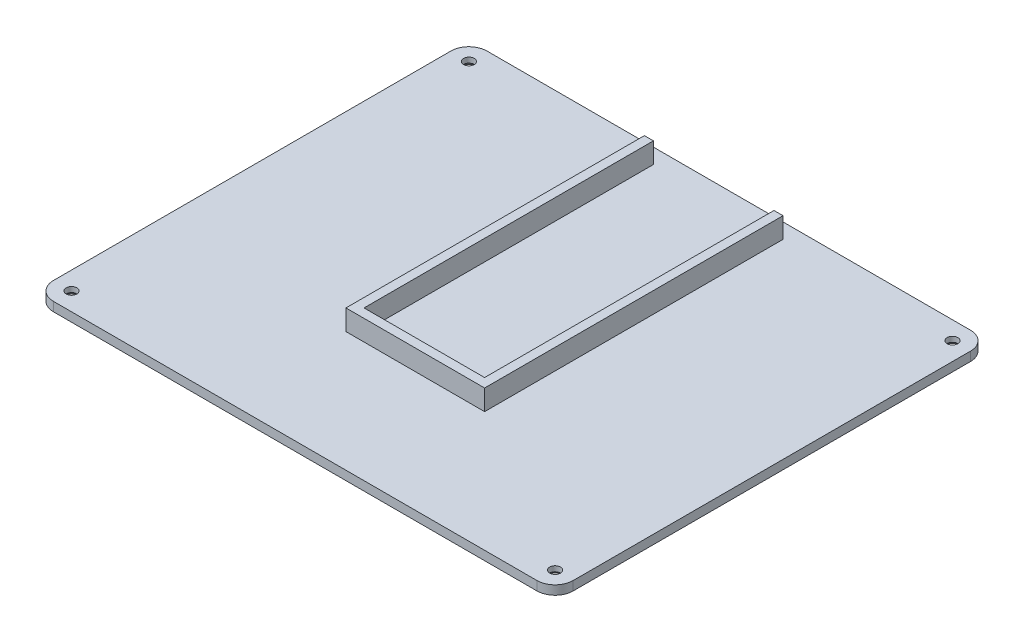
SolidWorks part; units mm, degrees
material "ABS"
ref_plane "Front" through (0, 0, 0) normal (0, 0, 1) x (1, 0, 0)
ref_plane "Top" through (0, 0, 0) normal (0, 1, 0) x (1, 0, 0)
ref_plane "Right" through (0, 0, 0) normal (1, 0, 0) x (0, 0, -1)
sketch "Sketch1" plane through (0, 0, 0) normal (0, 1, 0) x (1, 0, 0)
  line L1 (-43.1005, 35.9565) -> (43.1005, 35.9565)
  line L2 (-43.1005, 35.9565) -> (-43.1005, -35.9565)
  line L3 (-43.1005, -35.9565) -> (43.1005, -35.9565)
  line L4 (43.1005, 35.9565) -> (43.1005, -35.9565)
  line L5 (-43.1005, 35.9565) -> (43.1005, -35.9565) construction
  line L6 (-43.1005, -35.9565) -> (43.1005, 35.9565) construction
  point P0 (0, 0)
  dimension "D1" = 71.913
  dimension "D2" = 86.201
extrude "Boss-Extrude1" add sketch "Sketch1" along normal blind 1.5
fillet "Fillet1" radius 3 4 edges at (-43.1005, 0.75, 35.9565) (-43.1005, 0.75, -35.9565) (43.1005, 0.75, -35.9565) (43.1005, 0.75, 35.9565)
hole_wizard "#2-56 Tapped Hole1" positions "Sketch2" profile "Sketch4" tap size "#2-56" standard "ANSI Inch" end condition through all
sketch "Sketch2" plane through (0, 0, 0) normal (0, -1, 0) x (-1, 0, 0)
  point P0 (40.1005, -32.9565)
  point P3 (-40.1005, -32.9565)
  point P6 (-40.1005, 32.9565)
  point P9 (40.1005, 32.9565)
sketch "Sketch4" plane through (-40.1005, 0, 32.9565) normal (1, 0, 0) x (0, 0, -1)
  line L0 (0, 0) -> (0, 1.5)
  line L1 (0, 1.5) -> (0.889, 1.5)
  line L2 (0.889, 1.5) -> (0.889, 0.635)
  line L3 (0.889, 0.635) -> (1.524, 0)
  line L5 (1.524, 0) -> (0, 0)
  line L6 (-0.889, 0.635) -> (-1.524, 0) construction
  line L11 (0, -6.35) -> (0, 107.95) construction
  dimension "Thru Tap Drill Dia." = 1.778
  dimension "Thru Tap Drill Depth" = 1.5
  dimension "Near C'Sink Dia." = 3.048
  dimension "Near C'Sink Angle" = 90
cosmetic thread "Hole Thread1" parameters "D2"=2.1844
cosmetic thread "Hole Thread2" parameters "D2"=2.1844
cosmetic thread "Hole Thread3" parameters "D2"=2.1844
cosmetic thread "Hole Thread4" parameters "D2"=2.1844
sketch "Sketch5" plane through (0, 1.5, 0) normal (0, 1, 0) x (1, 0, 0)
  line L0 (-10, 35.9565) -> (-10, -14.5435)
  line L1 (40.1005, 35.9565) -> (-40.1005, 35.9565) construction
  line L2 (-10, -14.5435) -> (10, -14.5435)
  line L3 (10, -14.5435) -> (10, 35.9565)
  line L4 (10, 35.9565) -> (11.5, 35.9565)
  line L5 (11.5, 35.9565) -> (11.5, -16.0435)
  line L6 (11.5, -16.0435) -> (-11.5, -16.0435)
  line L7 (-11.5, -16.0435) -> (-11.5, 35.9565)
  line L8 (-11.5, 35.9565) -> (-10, 35.9565)
  line L9 (0, -14.5435) -> (0, 0) construction
  line L10 (-11.5, 33.4565) -> (-10, 33.4565)
  line L11 (10, 33.4565) -> (11.5, 33.4565)
  dimension "D1" = 50.5
  dimension "D2" = 1.5
  dimension "D3" = 1.5
  dimension "D4" = 20
  dimension "D5" = 2.5
extrude "Boss-Extrude2" add sketch "Sketch5" along normal blind 3.4 contours L11 L3 L2 L0 L10 L7 L6 L5 region at (-10.5458, 1.5, -9.4565)
